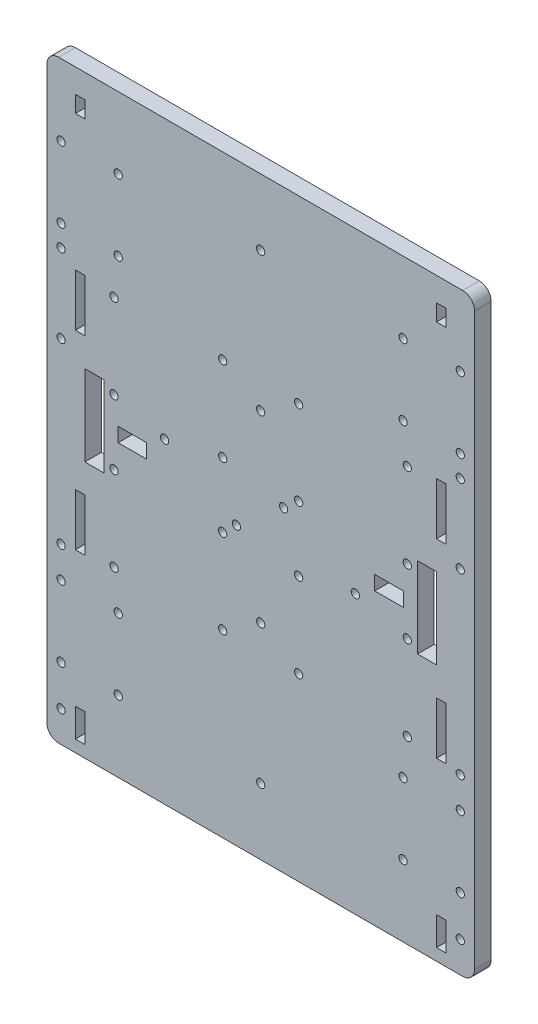
SolidWorks part; units mm, degrees
ref_plane "Front Plane" through (0, 0, 0) normal (0, 0, 1) x (1, 0, 0)
ref_plane "Top Plane" through (0, 0, 0) normal (0, 1, 0) x (1, 0, 0)
ref_plane "Right Plane" through (0, 0, 0) normal (1, 0, 0) x (0, 0, -1)
sketch "Sketch1" plane through (0, 0, 0) normal (0, 0, 1) x (1, 0, 0)
  line L1 (-90, 125) -> (90, 125)
  line L2 (-90, 125) -> (-90, -125)
  line L3 (-90, -125) -> (90, -125)
  line L4 (90, 125) -> (90, -125)
  line L5 (-90, 125) -> (90, -125) construction
  line L6 (-90, -125) -> (90, 125) construction
  point P0 (0, 0)
  dimension "D1" = 250
  dimension "D2" = 180
extrude "Boss-Extrude1" add sketch "Sketch1" along normal blind 7
fillet "Fillet1" radius 5 4 edges at (90, -125, 3.5) (-90, -125, 3.5) (-90, 125, 3.5) (90, 125, 3.5)
sketch "Sketch4" plane through (0, 0, 0) normal (0, 0, -1) x (-1, 0, 0)
  line L0 (0, 125) -> (0, -125)
  line L1 (-85, 125) -> (85, 125) construction
  line L2 (85, -125) -> (-85, -125) construction
  line L5 (0, 94.96) -> (-59.94, 94.96)
  line L6 (-59.94, 94.96) -> (-84, 94.96)
  line L10 (-84, 94.96) -> (-84, 65.04)
  line L11 (-59.94, 94.96) -> (-59.94, 65.04)
  circle A1 centre (-59.94, 94.96) radius 1.73
  circle A2 centre (-84, 94.96) radius 1.73
  circle A3 centre (-84, 65.04) radius 1.73
  circle A4 centre (-59.94, 65.04) radius 1.73
  dimension "D3" = 59.94
  dimension "D5" = 3.46
  dimension "D6" = 3.46
  dimension "D7" = 3.46
  dimension "D8" = 3.46
  dimension "D4" = 24.06
extrude "Cut-Extrude2" cut sketch "Sketch4" against normal up to surface (7 mm away) contours A2 | A1 | A3 | A4 up to face at (0, 0, 7)
mirror "Mirror3" about plane through (0, 0, 0) normal (1, 0, 0) of "Cut-Extrude2"
mirror "Mirror4" about plane through (0, 0, 0) normal (0, 1, 0) of "Cut-Extrude2", "Mirror3"
sketch "Sketch6" plane through (0, 0, 0) normal (0, 0, -1) x (-1, 0, 0)
  line L0 (-90, 0) -> (90, 0)
  line L1 (-90, -120) -> (-90, 120) construction
  line L2 (90, 120) -> (90, -120) construction
  line L3 (0, 125) -> (0, -125)
  line L4 (-85, 125) -> (85, 125) construction
  line L5 (85, -125) -> (-85, -125) construction
  line L6 (66.6367, 0) -> (66.6367, -13.64)
  line L7 (90, -13.64) -> (61.71, -13.64)
  line L8 (61.71, -13.64) -> (61.71, -49.2)
  line L9 (61.71, -49.2) -> (15.99, -49.2)
  line L10 (15.99, -49.2) -> (15.99, -13.64)
  circle A0 centre (61.71, -13.64) radius 1.73
  circle A1 centre (15.99, -13.64) radius 1.73
  circle A2 centre (15.99, -49.2) radius 1.73
  circle A3 centre (61.71, -49.2) radius 1.73
  dimension "D3" = 3.46
  dimension "D4" = 35.56
  dimension "D7" = 3.46
  dimension "D8" = 3.46
  dimension "D9" = 3.46
  dimension "D1" = 13.64
  dimension "D2" = 28.29
  dimension "D5" = 45.72
  dimension "D6" = 35.56
extrude "Cut-Extrude3" cut sketch "Sketch6" against normal up to surface (7 mm away) contours A2 | A3 | A0 | A1 up to face at (-58.21, -94.96, 7)
mirror "Mirror5" about plane through (0, 0, 0) normal (1, 0, 0) of "Cut-Extrude3"
mirror "Mirror7" about plane through (0, 0, 0) normal (0, 1, 0) of "Mirror5"
sketch "Sketch7" plane through (0, 0, 0) normal (0, 0, -1) x (-1, 0, 0)
  line L0 (-9.6358, 0) -> (-9.6358, -8.125)
  line L1 (-90, 0) -> (90, 0) construction
  line L2 (0, -8.125) -> (-10.22, -8.125)
  line L3 (0, 125) -> (0, -125) construction
  line L4 (-9.6358, 0) -> (-9.6358, 8.125)
  line L5 (-9.6358, 8.125) -> (-39.8358, 8.125)
  line L6 (7.3254, 0) -> (7.3254, 8.125)
  line L7 (0, 8.125) -> (10.22, 8.125)
  line L8 (10.22, 8.125) -> (10.22, -8.125)
  line L9 (10.22, -8.125) -> (40.42, -8.125)
  line L10 (-39.8358, 8.125) -> (-39.8358, -8.125)
  line L11 (40.42, -8.125) -> (40.42, 8.125)
  circle A0 centre (-10.22, -8.125) radius 1.73
  circle A1 centre (-39.8358, 8.125) radius 1.73
  circle A2 centre (10.22, 8.125) radius 1.73
  circle A3 centre (40.42, -8.125) radius 1.73
  circle A4 centre (-9.6358, 8.125) radius 1.73
  circle A5 centre (10.22, -8.125) radius 1.73
  circle A6 centre (-39.8358, -8.125) radius 1.73
  circle A7 centre (40.42, 8.125) radius 1.73
  dimension "D3" = 3.46
  dimension "D4" = 8.125
  dimension "D6" = 3.46
  dimension "D10" = 3.46
  dimension "D11" = 3.46
  dimension "D12" = 3.46
  dimension "D13" = 3.46
  dimension "D14" = 3.46
  dimension "D16" = 3.46
  dimension "D1" = 8.125
  dimension "D2" = 10.22
  dimension "D5" = 30.2
  dimension "D7" = 8.125
  dimension "D8" = 10.22
  dimension "D9" = 30.2
  dimension "D15" = 16.25
extrude "Cut-Extrude5" cut sketch "Sketch7" against normal up to surface (7 mm away) contours A6 | A4 | A7 | A5 up to face at (-14.26, 13.64, 7)
sketch "Sketch8" plane through (0, 0, 0) normal (0, 0, -1) x (-1, 0, 0)
  line L0 (-33.2449, 0) -> (-33.2449, -33.91)
  line L1 (-90, 0) -> (90, 0) construction
  line L2 (0, -33.91) -> (-27.145, -33.91)
  line L3 (0, 125) -> (0, -125) construction
  line L4 (-30.605, -33.91) -> (-33.2449, -33.91)
  line L6 (28.875, -35.64) -> (28.875, -87.43)
  line L7 (55, 0) -> (-55, 0) construction
  line L8 (-30.605, -33.91) -> (-33.2449, -33.91)
  line L10 (-30.605, -33.91) -> (-33.2449, -33.91)
  line L35 (0, -33.91) -> (-27.145, -33.91)
  circle A0 centre (28.875, -33.91) radius 1.73
  circle A1 centre (-28.875, -33.91) radius 1.73
  circle A2 centre (-28.875, -89.16) radius 1.73
  circle A3 centre (28.875, -89.16) radius 1.73
  circle A4 centre (-28.875, 89.16) radius 1.73
  circle A5 centre (28.875, 89.16) radius 1.73
  circle A6 centre (28.875, 33.91) radius 1.73
  circle A7 centre (-28.875, 33.91) radius 1.73
  circle A8 centre (-43.875, -33.91) radius 1.73
  circle A9 centre (13.875, -33.91) radius 1.73
  circle A10 centre (-43.875, -89.16) radius 1.73
  circle A11 centre (13.875, -89.16) radius 1.73
  circle A12 centre (-43.875, 33.91) radius 1.73
  circle A13 centre (-43.875, 89.16) radius 1.73
  circle A14 centre (13.875, 89.16) radius 1.73
  circle A15 centre (13.875, 33.91) radius 1.73
  dimension "D6" = 3.46
  dimension "D7" = 3.46
  dimension "D8" = 3.46
  dimension "D9" = 3.46
  dimension "D13" = 3.46
  dimension "D14" = 3.46
  dimension "D15" = 3.46
  dimension "D16" = 3.46
  dimension "D17" = 3.46
  dimension "D18" = 3.46
  dimension "D19" = 3.46
  dimension "D20" = 3.46
  dimension "D1" = 33.91
  dimension "D2" = 28.875
  dimension "D3" = 28.875
  dimension "D4" = 55.25
  dimension "D5" = 55.25
  dimension "D11" = 15
  dimension "D12" = 57.75
sketch "Sketch9" plane through (0, 0, 0) normal (0, 0, -1) x (-1, 0, 0)
  line L0 (90, 0) -> (74, 0)
  line L1 (-90, 0) -> (90, 0) construction
  line L2 (74, 0) -> (74, 17)
  line L3 (74, 17) -> (66, 17)
  line L4 (66, 17) -> (66, -17)
  line L5 (66, -17) -> (74, -17)
  line L6 (74, -17) -> (74, 0)
  line L7 (90, 0) -> (60, 0)
  line L13 (60, 0) -> (60, 3)
  line L14 (60, 3) -> (48, 3)
  line L15 (48, 3) -> (48, -3)
  line L16 (48, -3) -> (60, -3)
  line L17 (60, -3) -> (60, 0)
  line L18 (74, 0) -> (74, -17)
  dimension "D9" = 12
  dimension "D1" = 16
  dimension "D2" = 17
  dimension "D3" = 8
  dimension "D4" = 30
  dimension "D5" = 8
  dimension "D6" = 3
  dimension "D7" = 12
  dimension "D8" = 6
extrude "Cut-Extrude8" cut sketch "Sketch9" against normal up to surface (7 mm away) contours L13 L14 L15 L16 L17 | L2 L3 L4 L5 L6 up to face at (41.5658, -8.125, 7)
mirror "Mirror9" about plane through (0, 0, 0) normal (1, 0, 0) of "Cut-Extrude8"
sketch "Sketch10" plane through (0, 0, 7) normal (0, 0, 1) x (1, 0, 0)
  line L0 (84, 65.04) -> (84, -65.04)
  line L1 (84, 65.04) -> (84, 94.96)
  line L2 (84, -65.04) -> (84, -94.96)
  line L3 (84, -94.96) -> (84, -125)
  line L4 (-85, -125) -> (85, -125) construction
  line L5 (84, 94.96) -> (84, 125)
  line L6 (85, 125) -> (-85, 125) construction
  line L7 (84, 125) -> (84, 115)
  line L8 (84, 115) -> (82, 115)
  line L9 (82, 115) -> (82, 108)
  line L10 (82, 108) -> (86, 108)
  line L11 (86, 108) -> (86, 115)
  line L12 (86, 115) -> (84, 115)
  line L13 (84, 0) -> (84, 29)
  line L14 (84, 29) -> (82, 29)
  line L15 (82, 29) -> (82, 51)
  line L16 (82, 51) -> (86, 51)
  line L17 (86, 51) -> (86, 29)
  line L18 (84, 0) -> (84, -29)
  line L19 (84, -29) -> (86, -29)
  line L20 (86, -29) -> (86, -51)
  line L21 (86, -51) -> (82, -51)
  line L22 (82, -51) -> (82, -29)
  line L23 (82, -29) -> (84, -29)
  line L24 (84, -125) -> (84, -120)
  line L25 (84, -120) -> (82, -120)
  line L26 (82, -120) -> (82, -108)
  line L27 (82, -108) -> (86, -108)
  line L28 (86, -108) -> (86, -120)
  line L29 (86, -120) -> (84, -120)
  line L30 (86, 115) -> (86, -120)
  line L31 (86, 108) -> (86, 51)
  line L32 (84, 115) -> (86, 115)
  line L33 (84, 29) -> (85.6027, 29)
  line L34 (84, 29) -> (86, 29)
  line L35 (82, 51) -> (86, 51)
  line L36 (86, 29) -> (82, 29)
  line L37 (82, 29) -> (82, 51)
  line L38 (82, -29) -> (86, -29)
  line L39 (86, -29) -> (86, -51)
  line L40 (82, -51) -> (82, -29)
  line L41 (82, -108) -> (86, -108)
  line L42 (86, -120) -> (82, -120)
  line L43 (82, -120) -> (82, -108)
  line L44 (74, 0) -> (74, 125)
  line L45 (74, -17) -> (74, 17) construction
  line L46 (74, 0) -> (74, -125)
  line L47 (74, 115) -> (78, 115)
  line L48 (78, 115) -> (78, 108)
  line L49 (78, 108) -> (74, 108)
  line L50 (74, 108) -> (74, 115)
  line L51 (74, 51) -> (78, 51)
  line L52 (78, 51) -> (78, 29)
  line L53 (78, 29) -> (74, 29)
  line L54 (74, 29) -> (74, 51)
  line L55 (74, -29) -> (78, -29)
  line L56 (78, -29) -> (78, -51)
  line L57 (78, -51) -> (74, -51)
  line L58 (74, -51) -> (74, -29)
  line L59 (74, -108) -> (78, -108)
  line L60 (78, -108) -> (78, -120)
  line L61 (78, -120) -> (74, -120)
  line L62 (74, -120) -> (74, -108)
  dimension "D16" = 29
  dimension "D27" = 4
  dimension "D1" = 30.04
  dimension "D2" = 29.92
  dimension "D3" = 130.08
  dimension "D4" = 29.92
  dimension "D5" = 30.04
  dimension "D6" = 10
  dimension "D7" = 2
  dimension "D8" = 7
  dimension "D9" = 4
  dimension "D10" = 7
  dimension "D11" = 29
  dimension "D12" = 2
  dimension "D13" = 22
  dimension "D14" = 4
  dimension "D15" = 22
  dimension "D17" = 2
  dimension "D18" = 22
  dimension "D19" = 4
  dimension "D20" = 22
  dimension "D21" = 5
  dimension "D22" = 2
  dimension "D23" = 12
  dimension "D24" = 4
  dimension "D25" = 12
  dimension "D26" = 235
  dimension "D28" = 4
  dimension "D29" = 22
  dimension "D30" = 4
  dimension "D31" = 4
  dimension "D32" = 22
  dimension "D33" = 4
  dimension "D34" = 4
  dimension "D35" = 12
sketch "Sketch13" plane through (0, 0, 7) normal (0, 0, 1) x (1, 0, 0)
  line L0 (84, 29) -> (86, 29)
sketch "Sketch15" plane through (0, 0, 7) normal (0, 0, 1) x (1, 0, 0)
  line L0 (74, 17) -> (74, 125)
  line L1 (85, 125) -> (-85, 125) construction
  line L2 (74, -17) -> (74, -125)
  line L3 (-85, -125) -> (85, -125) construction
extrude "Cut-Extrude14" cut sketch "Sketch10" against normal up to surface (7 mm away) contours L48 L49 L50 L47 up to face at (70, 0, 0)
extrude "Cut-Extrude15" cut sketch "Sketch10<9>" against normal up to surface (7 mm away) contours L52 L53 L54 L51 up to face at (54, 0, 0)
sketch "Sketch10<9>" plane through (0, 0, 7) normal (0, 0, 1) x (1, 0, 0) same geometry as "Sketch10"
extrude "Cut-Extrude16" cut sketch "Sketch10<10>" against normal up to surface (7 mm away) contours L55 L56 L57 L58 up to face at (76, 111.5, 0)
sketch "Sketch10<10>" plane through (0, 0, 7) normal (0, 0, 1) x (1, 0, 0) same geometry as "Sketch10"
extrude "Cut-Extrude17" cut sketch "Sketch10<11>" against normal up to surface (7 mm away) contours L60 L61 L62 L59 up to face at (76, 40, 0)
sketch "Sketch10<11>" plane through (0, 0, 7) normal (0, 0, 1) x (1, 0, 0) same geometry as "Sketch10"
mirror "Mirror11" about plane through (0, 0, 0) normal (1, 0, 0) of "Cut-Extrude14", "Cut-Extrude15", "Cut-Extrude16", "Cut-Extrude17"
sketch "Sketch16" plane through (0, 0, 7) normal (0, 0, 1) x (1, 0, 0)
  line L0 (84, -120) -> (84, -112)
  line L1 (84, -94.96) -> (84, -125) construction
  line L2 (84, -112) -> (84, -52)
  line L3 (84, 65.04) -> (84, -65.04) construction
  line L4 (84, -52) -> (84, 23)
  line L5 (84, 23) -> (84, 56)
  circle A0 centre (84, -112) radius 1.73
  circle A1 centre (84, -52) radius 1.73
  circle A2 centre (84, 23) radius 1.73
  circle A3 centre (84, 56) radius 1.73
  dimension "D2" = 3.46
  dimension "D4" = 3.46
  dimension "D6" = 3.46
  dimension "D8" = 3.46
  dimension "D1" = 8
  dimension "D3" = 60
  dimension "D5" = 75
  dimension "D7" = 33
extrude "Cut-Extrude18" cut sketch "Sketch16" against normal up to surface (7 mm away) contours A0 | A1 | A2 | A3 up to face at (-76, -114, 0)
mirror "Mirror12" about plane through (0, 0, 0) normal (1, 0, 0) of "Cut-Extrude18"
sketch "Sketch17" plane through (0, 0, 0) normal (0, 0, -1) x (-1, 0, 0)
  line L2 (28.875, -97.16) -> (-28.875, -97.16)
  line L3 (0, -97.16) -> (0, -38.66)
  line L6 (1.73, 97.16) -> (-1.73, 97.16)
  line L7 (0, 97.16) -> (0, 38.66)
  circle A0 centre (0, -97.16) radius 1.73
  circle A1 centre (0, -38.66) radius 1.73
  circle A2 centre (0, 97.16) radius 1.73
  circle A3 centre (0, 38.66) radius 1.73
  dimension "D3" = 3.46
  dimension "D5" = 3.46
  dimension "D8" = 3.46
  dimension "D10" = 3.46
  dimension "D4" = 58.5
  dimension "D9" = 58.5
extrude "Cut-Extrude19" cut sketch "Sketch17" against normal up to surface (7 mm away) contours A0 | A1 | A3 | A2 up to face at (-85.73, -112, 7)
